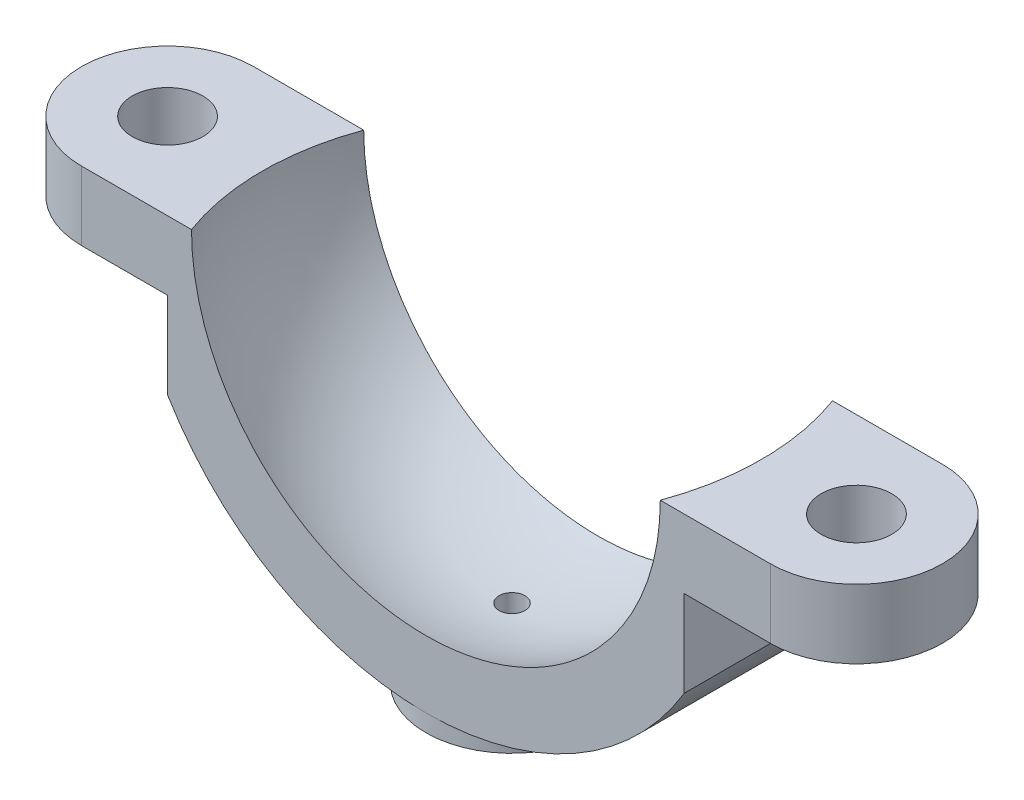
SolidWorks part; units mm, degrees
material "Сталь 40Х13 ГОСТ 5632-72"
ref_plane "Спереди" through (0, 0, 0) normal (0, 0, 1) x (1, 0, 0)
ref_plane "Сверху" through (0, 0, 0) normal (0, 1, 0) x (1, 0, 0)
ref_plane "Справа" through (0, 0, 0) normal (1, 0, 0) x (0, 0, -1)
sketch "Эскиз1" plane through (0, 0, 0) normal (0, 0, 1) x (1, 0, 0)
  line L0 (-35, 0) -> (35, 0)
  circle A0 centre (0, 0) radius 24
  circle A1 centre (0, 0) radius 35
  circle A2 centre (0, 0) radius 26
  dimension "D1" = 48
  dimension "D2" = 70
  dimension "D3" = 52
extrude "Бобышка-Вытянуть2" add sketch "Эскиз1" along normal mid plane 38 contours A2 L0 A1 | L0 A2 A0 region at (25, -0.5814, 0) region at (30.5, -0.7826, 0)
sketch "Эскиз2" plane through (0, 0, 0) normal (0, 1, 0) x (1, 0, 0)
  line L0 (40, 10) -> (30, 10)
  line L1 (30, 10) -> (30, 0)
  line L2 (30, 0) -> (30, -10)
  line L3 (30, -10) -> (40, -10)
  circle A0 centre (40, 0) radius 10
  line M4 (35, -19) -> (35, 19)
  dimension "D1" = 20
  dimension "D2" = 40
extrude "Бобышка-Вытянуть3" add sketch "Эскиз2" against normal blind 40 contours A0 M4 | A0 L0 M4 | A0 L3 M4 | A0 L0 L1 M4 | A0 L2 L3 M4 | A0 region at (36.2326, 0, -9.6032) region at (31.784, 0, -7.5598) region at (32.9498, 0, 0) region at (36.2326, 0, 9.6032) region at (31.784, 0, 7.5598)
sketch "Эскиз3" plane through (0, -40, 0) normal (0, -1, 0) x (1, 0, 0)
  line L3 (40, 10) -> (30, 10)
  line L4 (40, 10) -> (30, 10)
  line L5 (30, 10) -> (30, -10)
  line L6 (30, 10) -> (30, -10)
  line L7 (30, -10) -> (40, -10)
  line L8 (30, -10) -> (40, -10)
  arc A1 (40, -10) -> (40, 10) centre (40, 0) ccw
  arc A2 (40, -10) -> (40, 10) centre (40, 0) ccw
  dimension "D1" = 0
extrude "Вырез-Вытянуть1" cut sketch "Эскиз3" against normal offset from surface (32 mm away) 8 up to face at (-29.5, 0, 0)
sketch "Эскиз4" plane through (0, -8, 0) normal (0, -1, 0) x (1, 0, 0)
  circle A0 centre (40, 0) radius 4.1
  dimension "D1" = 8.2
extrude "Вырез-Вытянуть2" cut sketch "Эскиз4" against normal through all
mirror "Зеркальное отражение1" about plane through (0, 0, 0) normal (1, 0, 0) of "Вырез-Вытянуть2", "Вырез-Вытянуть1", "Бобышка-Вытянуть3"
sketch "Эскиз5" plane through (0, 0, 0) normal (0, 1, 0) x (1, 0, 0)
  circle A0 centre (0, 0) radius 10
  circle A1 centre (0, 0) radius 1.5
  dimension "D1" = 20
  dimension "D2" = 3
extrude "Бобышка-Вытянуть4" add sketch "Эскиз5" along normal up to surface (2 mm away) from offset 37 contours A0 A1 | A1 region at (-9.7172, 0, 0) region at (0, 0, 0) up to face at (0, -10.9282, 0) offset against normal yes
extrude "Вырез-Вытянуть3" cut sketch "Эскиз5<4>" against normal through all contours A1 region at (0, 0, 0)
sketch "Эскиз5<4>" plane through (0, 0, 0) normal (0, 1, 0) x (1, 0, 0) same geometry as "Эскиз5"
extrude "Вырез-Вытянуть4" cut sketch "Эскиз1<4>" against normal mid plane 24 contours L0 A2 A0 region at (25, -0.5814, 0)
sketch "Эскиз1<4>" plane through (0, 0, 0) normal (0, 0, 1) x (1, 0, 0) same geometry as "Эскиз1"
sketch "Эскиз6" plane through (0, 0, 0) normal (0, 1, 0) x (1, 0, 0)
  circle A0 centre (0, 0) radius 4
  dimension "D1" = 8
extrude "Вырез-Вытянуть5" cut sketch "Эскиз6" against normal blind 30
sketch "Эскиз7" plane through (0, 0, 0) normal (0, 0, 1) x (1, 0, 0)
  line L0 (0, 0) -> (0, 48.4506) construction
  line L1 (0, 33) -> (0, -33)
  arc A0 (0, -33) -> (0, 33) centre (0, 0) ccw
  dimension "D1" = 66
revolve "Повернуть1" add sketch "Эскиз7" angle 360 about L0
sketch "Эскиз8" plane through (0, 0, 0) normal (0, 0, 1) x (1, 0, 0)
  line L0 (0, 0) -> (0, 44.6529) construction
  line L1 (0, 29) -> (0, -29)
  arc A0 (0, -29) -> (0, 29) centre (0, 0) ccw
  dimension "D1" = 58
revolve "Вырез-Повернуть1" cut sketch "Эскиз8" angle 360 about L0
sketch "Эскиз10" plane through (0, 0, -10) normal (0, 0, -1) x (-1, 0, 0)
  line L0 (-40, -8) -> (-40, 0) construction
  line L1 (-40, -35) -> (40, -35)
  line L2 (-40, -35) -> (-40, 33)
  line L3 (-40, 33) -> (40, 33)
  line L4 (40, -35) -> (40, 33)
  line L5 (40, -8) -> (40, 0) construction
  arc A0 (33, 0) -> (-33, 0) centre (0, 0) ccw construction
  arc A1 (-35, 0) -> (35, 0) centre (0, 0) ccw construction
extrude "Вырез-Вытянуть6" cut sketch "Эскиз10" along normal through all
mirror "Зеркальное отражение2" about plane through (0, 0, 0) normal (0, 0, 1) of "Вырез-Вытянуть6"
sketch "Эскиз11" plane through (0, 0, 0) normal (0, 1, 0) x (1, 0, 0)
  line L1 (-40, 10) -> (40, 10)
  line L2 (-40, 10) -> (-40, -10)
  line L3 (-40, -10) -> (40, -10)
  line L4 (40, 10) -> (40, -10)
  arc A0 (-40, 10) -> (-40, -10) centre (-40, 0) ccw construction
extrude "Вырез-Вытянуть7" cut sketch "Эскиз11" along normal through all
sketch "Эскиз12" plane through (0, -8, 0) normal (0, -1, 0) x (1, 0, 0)
  line L1 (-40, 10) -> (-30, 10)
  line L2 (-40, 10) -> (-40, -10)
  line L3 (-40, -10) -> (-30, -10)
  line L4 (-30, 10) -> (-30, -10)
extrude "Вырез-Вытянуть8" cut sketch "Эскиз12" along normal through all
sketch "Эскиз13" plane through (0, -8, 0) normal (0, -1, 0) x (1, 0, 0)
  line L1 (30, 10) -> (40, 10)
  line L2 (30, 10) -> (30, -10)
  line L3 (30, -10) -> (40, -10)
  line L4 (40, 10) -> (40, -10)
extrude "Вырез-Вытянуть9" cut sketch "Эскиз13" along normal through all
sketch "Эскиз14" plane through (0, -37, 0) normal (0, -1, 0) x (1, 0, 0)
  circle A0 centre (0, 0) radius 1.5 construction
  circle A1 centre (0, 0) radius 1.5
extrude "Вырез-Вытянуть10" cut sketch "Эскиз14" against normal through all
